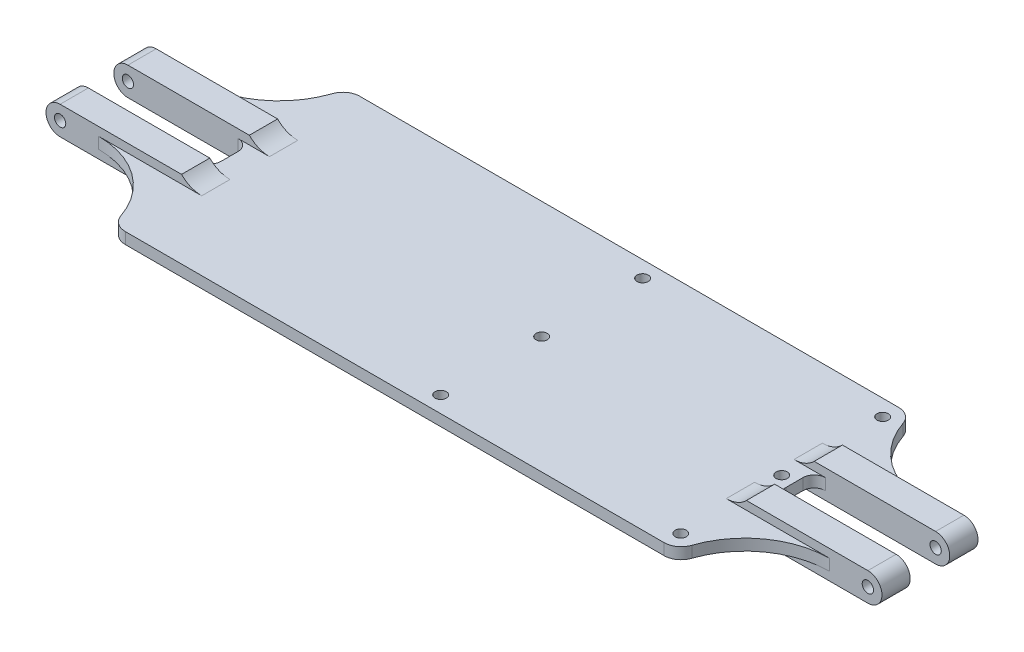
SolidWorks part; units mm, degrees
ref_plane "Front Plane" through (0, 0, 0) normal (0, 0, 1) x (1, 0, 0)
ref_plane "Top Plane" through (0, 0, 0) normal (0, 1, 0) x (1, 0, 0)
ref_plane "Right Plane" through (0, 0, 0) normal (1, 0, 0) x (0, 0, -1)
sketch "Sketch1" plane through (0, 0, 0) normal (0, 1, 0) x (1, 0, 0)
  line L0 (0, 121.3543) -> (0, -121.3543) construction
  line L1 (-100, -41.5) -> (100, -41.5)
  line L2 (-100, -41.5) -> (-100, 41.5)
  line L3 (-100, 41.5) -> (100, 41.5)
  line L4 (100, -41.5) -> (100, 41.5)
  line L5 (-100, -41.5) -> (100, 41.5) construction
  line L6 (-100, 41.5) -> (100, -41.5) construction
  line L7 (-246.33, 0) -> (246.33, 0) construction
  line L8 (-100, 7) -> (-149, 7)
  line L9 (-149, 7) -> (-149, 17)
  line L10 (-149, 17) -> (-100, 17)
  line L11 (-149, -17) -> (-100, -17)
  line L12 (-149, -7) -> (-149, -17)
  line L13 (-100, -7) -> (-149, -7)
  line L14 (-143, 46.0679) -> (-143, -44.6537) construction
  line L15 (149, -17) -> (100, -17)
  line L16 (149, -7) -> (149, -17)
  line L17 (100, -7) -> (149, -7)
  line L18 (100, 7) -> (149, 7)
  line L19 (149, 7) -> (149, 17)
  line L20 (149, 17) -> (100, 17)
  circle A0 centre (95.5, 35.75) radius 2
  circle A1 centre (95.5, 0) radius 2
  circle A2 centre (95.5, -35.75) radius 2
  circle A3 centre (10.5, -35.75) radius 2
  circle A4 centre (10.5, 0) radius 2
  circle A5 centre (10.5, 35.75) radius 2
  point P0 (0, 0)
  point P8 (0, 0)
  point P11 (0, 0)
  dimension "D7" = 4
  dimension "D8" = 4
  dimension "D9" = 4
  dimension "D10" = 4
  dimension "D11" = 4
  dimension "D12" = 4
  dimension "D1" = 83
  dimension "D2" = 200
  dimension "D3" = 14
  dimension "D4" = 10
  dimension "D5" = 43
  dimension "D6" = 6
extrude "Boss-Extrude1" add sketch "Sketch1" along normal mid plane 10 contours L10 L9 L8 L2 | L2 L13 L12 L11 | L19 L20 L4 L18 | L17 L4 L15 L16 region at (-124.5, 0, 12) region at (124.5, 0, 12) region at (-124.5, 0, -12) region at (124.5, 0, -12)
sketch "Sketch2" plane through (0, 0, -17) normal (0, 0, -1) x (-1, 0, 0)
  line L0 (-149, -5) -> (-100, -5) construction
  line L1 (-149, 5) -> (-100, 5) construction
  line L2 (-149, 5) -> (-149, -5) construction
  line L6 (0, 69.849) -> (0, -80.9232) construction
  line L10 (-143, 5) -> (-143, 9.5057)
  line L11 (-143, 9.5057) -> (-152.7264, 9.5057)
  line L12 (-152.7264, 9.5057) -> (-152.7264, -6.9043)
  line L13 (-152.7264, -6.9043) -> (-143, -6.9043)
  line L14 (-143, -6.9043) -> (-143, -5)
  line L15 (143, 5) -> (143, 9.5057)
  line L16 (143, 9.5057) -> (152.7264, 9.5057)
  line L17 (152.7264, 9.5057) -> (152.7264, -6.9043)
  line L18 (152.7264, -6.9043) -> (143, -6.9043)
  line L19 (143, -6.9043) -> (143, -5)
  arc A0 (-143, -5) -> (-143, 5) centre (-143, 0) cw
  circle A1 centre (-143, 0) radius 2
  circle A2 centre (143, 0) radius 2
  arc A3 (143, -5) -> (143, 5) centre (143, 0) ccw
  dimension "D2" = 4
  dimension "D1" = 6
extrude "Cut-Extrude7" cut sketch "Sketch2" against normal through all both and the other way through all
extrude "Boss-Extrude2" add sketch "Sketch1<3>" along normal mid plane 4 contours L1 L4 L3 L2 region at (-0.2418, 0, 0)
sketch "Sketch1<3>" plane through (0, 0, 0) normal (0, 1, 0) x (1, 0, 0) same geometry as "Sketch1"
fillet "Fillet1" radius 10 4 edges at (-100, 2, -12) (-100, 2, 12) (100, 2, -12) (100, 2, 12)
sketch "Sketch3" plane through (0, -2, 0) normal (0, -1, 0) x (1, 0, 0)
  line L0 (-100, 17) -> (100, 17)
  line L1 (-100, 7) -> (100, 7)
  line L2 (-100, -7) -> (100, -7)
  line L3 (-100, -17) -> (100, -17)
  line L4 (-100, -17) -> (-100, -7)
  line L5 (100, -17) -> (100, -7)
  line L6 (100, 7) -> (100, 17)
  line L7 (-100, 7) -> (-100, 17)
extrude "Boss-Extrude3" add sketch "Sketch3" along normal up to surface (3 mm away) up to face at (121.5, -5, 13.25)
fillet "Fillet2" radius 30 4 edges at (-100, 0, 17) (-100, 0, -17) (100, 0, 17) (100, 0, -17)
fillet "Fillet3" radius 4 4 edges at (100, 0, 7) (100, 0, -7) (-100, 0, 7) (-100, 0, -7)
fillet "Fillet4" radius 6 4 edges at (100, 0, 41.5) (-100, 0, 41.5) (100, 0, -41.5) (-100, 0, -41.5)
